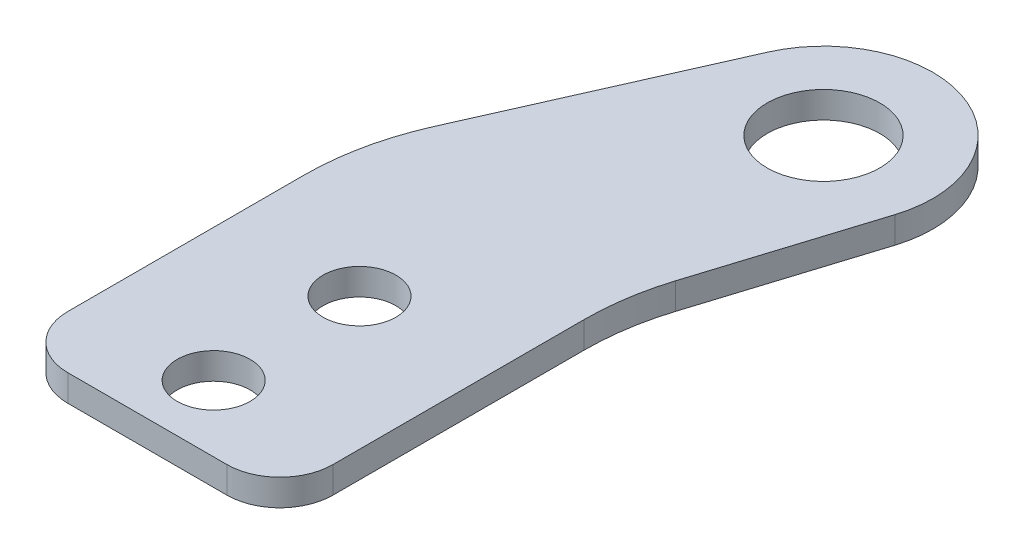
SolidWorks part; units mm, degrees
material "Plain Carbon Steel"
ref_plane "Front Plane" through (0, 0, 0) normal (0, 0, 1) x (1, 0, 0)
ref_plane "Top Plane" through (0, 0, 0) normal (0, 1, 0) x (1, 0, 0)
ref_plane "Right Plane" through (0, 0, 0) normal (1, 0, 0) x (0, 0, -1)
sketch "Sketch1" plane through (0, 0, 0) normal (0, 1, 0) x (1, 0, 0)
  line L0 (-10, 0) -> (10, 0)
  line L1 (10, 0) -> (10, 26)
  line L2 (10, 26) -> (14.8718, 41.5307)
  line L3 (-10, 0) -> (-10, 26)
  line L4 (-10, 26) -> (-0.5426, 47.3423)
  arc A0 (-0.5426, 47.3423) -> (14.8718, 41.5307) centre (7, 44) cw
  circle A1 centre (7, 44) radius 4.25
  dimension "D4" = 8.5
  dimension "D6" = 4
  dimension "D1" = 20
  dimension "D2" = 7
  dimension "D3" = 18
  dimension "D5" = 26
base flange "Base-Flange1" sketch "Sketch1" thickness 2 reverse thickness direction no parameters "D1"=2
fillet "Fillet1" radius 20 2 edges at (-10, -1, -26) (10, -1, -26)
hole_wizard "M5 Clearance Hole1" positions "Sketch6" profile "Sketch7" hole size "M5" standard "ISO" end condition through all
sketch "Sketch6" plane through (0, 0, 0) normal (0, 1, 0) x (1, 0, 0)
  line L0 (0, 0) -> (0, 5) construction
  line L1 (0, 5) -> (0, 16) construction
  point P0 (0, 16)
  point P2 (0, 5)
  dimension "D1" = 5
  dimension "D2" = 11
sketch "Sketch7" plane through (0, 0, -16) normal (1, 0, 0) x (0, 0, 1)
  line L0 (0, 0) -> (0, 2)
  line L1 (0, 2) -> (2.75, 2)
  line L2 (2.75, 2) -> (2.75, 0)
  line L5 (2.75, 0) -> (0, 0)
  line L11 (0, -6.35) -> (0, 107.95) construction
  dimension "Thru Hole Dia." = 5.5
  dimension "Thru Hole Depth" = 2
fillet "Fillet2" radius 4 2 edges at (-10, -1, 0) (10, -1, 0)
sketch "Bend-Lines1" [suppressed] plane through (0, 0, 0) normal (0, 1, 0) x (1, 0, 0)
sketch "Bounding-Box1" [suppressed] plane through (0, 0, 0) normal (0, 1, 0) x (1, 0, 0)
sheet metal parameters "Sheet-Metal1" thickness 2 parameters "D1"=2
flat pattern "Flat-Pattern1" [suppressed]
sketch "Bend-Lines2" plane through (0, 0, 0) normal (0, 1, 0) x (1, 0, 0)
sketch3d "Bounding-Box2" [suppressed]
  line L0 (-18.569, -33.8012, 0) -> (-13.1494, 8.9739, 0) construction
  line L1 (2.684, -36.494, 0) -> (8.1036, 6.2811, 0) construction
  line L2 (-18.569, -33.8012, 0) -> (2.684, -36.494, 0) construction
  line L3 (-13.1494, 8.9739, 0) -> (8.1036, 6.2811, 0) construction
sheet metal parameters "Sheet-Metal2" thickness 2 parameters "D1"=2
flat pattern "Flat-Pattern1"
sketch "Bend-Lines2" plane through (0, 0, 0) normal (0, 1, 0) x (1, 0, 0)
sketch3d "Bounding-Box2" [suppressed]
  line L0 (-19.9345, -43.118, 0) -> (-12.9097, 10.0281, 0) construction
  line L1 (2.2351, -46.0483, 0) -> (9.2599, 7.0978, 0) construction
  line L2 (-19.9345, -43.118, 0) -> (2.2351, -46.0483, 0) construction
  line L3 (-12.9097, 10.0281, 0) -> (9.2599, 7.0978, 0) construction
